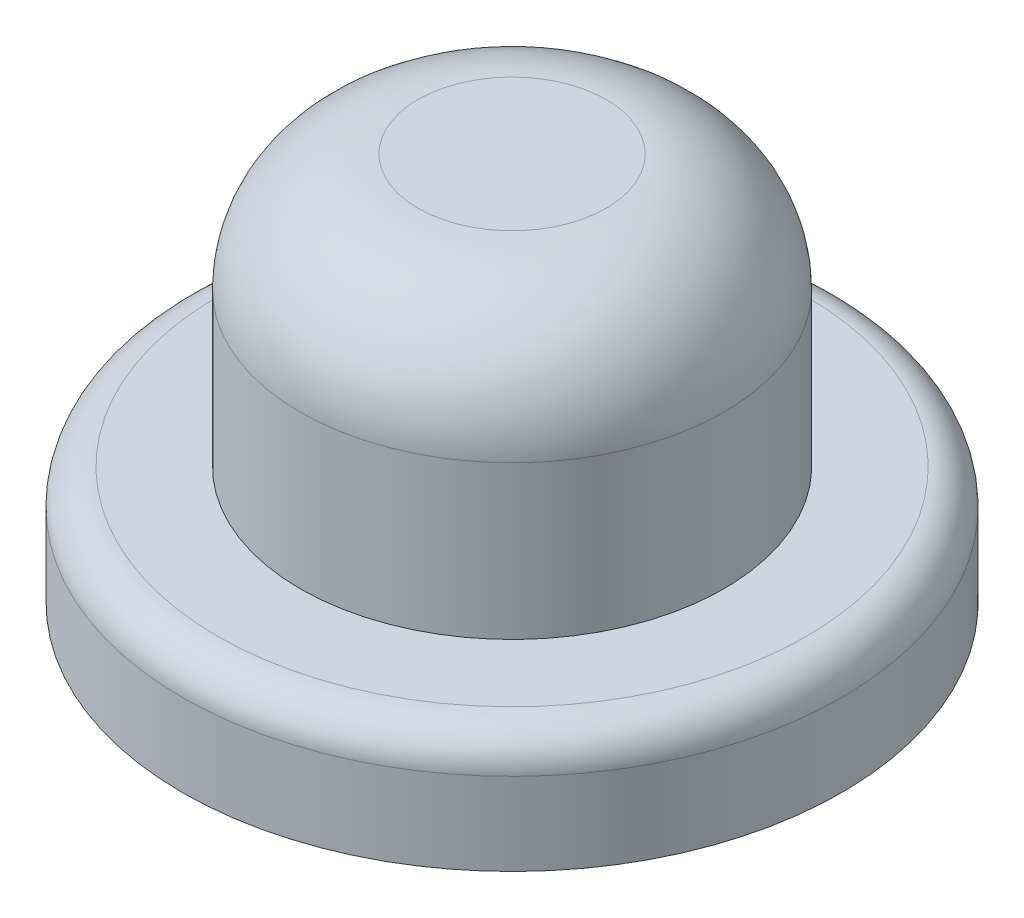
SolidWorks part; units mm, degrees
ref_plane "前视基准面" through (0, 0, 0) normal (0, 0, 1) x (1, 0, 0)
ref_plane "上视基准面" through (0, 0, 0) normal (0, 1, 0) x (1, 0, 0)
ref_plane "右视基准面" through (0, 0, 0) normal (1, 0, 0) x (0, 0, -1)
sketch "草图1" plane through (0, 0, 0) normal (0, 1, 0) x (1, 0, 0)
  circle A0 centre (0, 0) radius 2.8
  dimension "D1" = 5.6
extrude "凸台-拉伸2" add sketch "草图1" along normal blind 1
sketch "草图2" plane through (0, 1, 0) normal (0, 1, 0) x (1, 0, 0)
  circle A0 centre (0, 0) radius 1.8
  dimension "D1" = 3.6
extrude "凸台-拉伸3" add sketch "草图2" along normal blind 2.3
fillet "圆角1" radius 1 1 edges at (0, 3.3, 1.8)
fillet "圆角2" radius 0.3 1 edges at (0, 1, 2.8)
